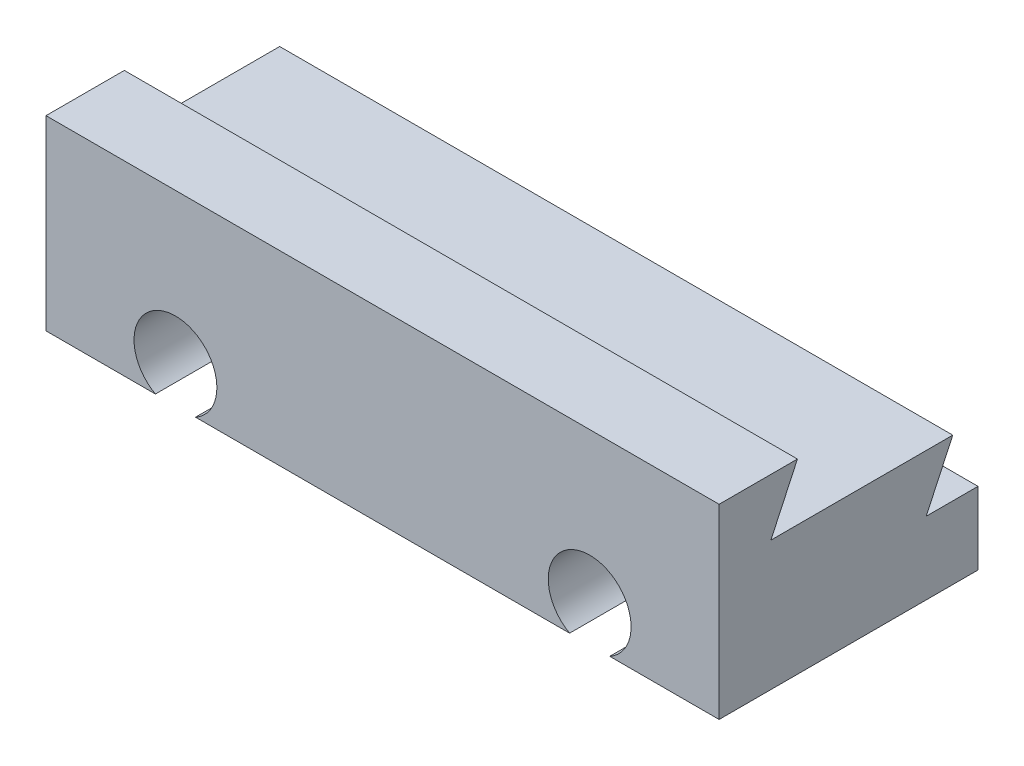
SolidWorks part; units mm, degrees
material "6061 Alloy"
ref_plane "Front Plane" through (0, 0, 0) normal (0, 0, 1) x (1, 0, 0)
ref_plane "Top Plane" through (0, 0, 0) normal (0, 1, 0) x (1, 0, 0)
ref_plane "Right Plane" through (0, 0, 0) normal (1, 0, 0) x (0, 0, -1)
sketch "Sketch1" plane through (0, 0, 0) normal (1, 0, 0) x (0, 0, -1)
  line L0 (0, 0) -> (0, 18)
  line L1 (0, 18) -> (7.5647, 18)
  line L2 (7.5647, 18) -> (5, 12.5)
  line L3 (5, 12.5) -> (22.5647, 12.5)
  line L4 (22.5647, 12.5) -> (20, 7)
  line L5 (20, 7) -> (25, 7)
  line L6 (25, 7) -> (25, 0)
  line L7 (25, 0) -> (0, 0)
  dimension "D1" = 65
  dimension "D2" = 65
  dimension "D3" = 5.5
  dimension "D4" = 5.5
  dimension "D5" = 7
  dimension "D6" = 5
  dimension "D7" = 20
  dimension "D8" = 5
extrude "Boss-Extrude1" add sketch "Sketch1" along normal blind 65
sketch "Sketch2" plane through (0, 0, -25) normal (0, 0, -1) x (-1, 0, 0)
  line L0 (-32.5, 7) -> (-32.5, 0) construction
  line L1 (-32.5, 3.5) -> (-12.5, 3.5) construction
  line L2 (-65, 7) -> (0, 7) construction
  line L3 (-65, 0) -> (0, 0) construction
  circle A0 centre (-12.5, 3.5) radius 2.1
  circle A1 centre (-52.5, 3.5) radius 2.1
  dimension "D2" = 4.2
  dimension "D1" = 20
  dimension "D3" = 3.5
extrude "Cut-Extrude1" cut sketch "Sketch2" against normal up to surface (25 mm away) up to face at (32.5, 9, 0)
sketch "Sketch3" plane through (0, 0, 0) normal (0, 0, 1) x (1, 0, 0)
  circle A0 centre (12.5, 3.5) radius 4
  circle A1 centre (52.5, 3.5) radius 4
  dimension "D1" = 8
extrude "Cut-Extrude2" cut sketch "Sketch3" against normal offset from surface (15 mm away) 10 up to face at (10.4, 3.5, -25)
